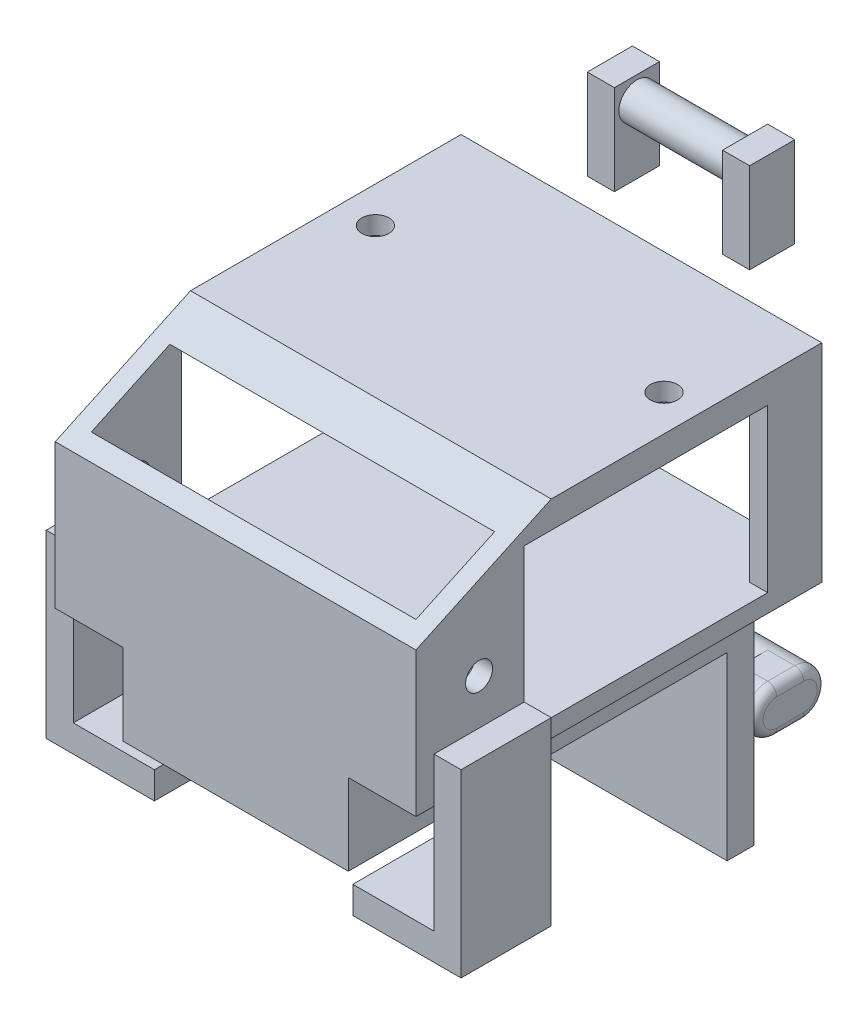
SolidWorks part; units mm, degrees
ref_plane "正面" through (0, 0, 0) normal (0, 0, 1) x (1, 0, 0)
ref_plane "平面" through (0, 0, 0) normal (0, 1, 0) x (1, 0, 0)
ref_plane "右側面" through (0, 0, 0) normal (1, 0, 0) x (0, 0, -1)
sketch "ｽｹｯﾁ1" plane through (0, 0, 0) normal (0, 1, 0) x (1, 0, 0)
  line L1 (0, 0) -> (25, 0)
  line L2 (0, 0) -> (0, 42)
  line L3 (0, 42) -> (25, 42)
  line L4 (25, 0) -> (25, 42)
  dimension "D1" = 25
  dimension "D2" = 42
extrude "ﾎﾞｽ - 押し出し1" add sketch "ｽｹｯﾁ1" along normal blind 9
sketch "ｽｹｯﾁ2" plane through (0, 0, -42) normal (0, 0, -1) x (-1, 0, 0)
  line L1 (-25, 9) -> (0, 9)
  line L2 (-25, 9) -> (-25, -20)
  line L3 (-25, -20) -> (0, -20)
  line L4 (0, 9) -> (0, -20)
  dimension "D1" = 29
extrude "ﾎﾞｽ - 押し出し2" add sketch "ｽｹｯﾁ2" along normal blind 3
sketch "ｽｹｯﾁ3" plane through (0, 9, 0) normal (0, 1, 0) x (1, 0, 0)
  line L1 (-7.5, 0) -> (32.5, 0)
  line L2 (-7.5, 0) -> (-7.5, 45)
  line L3 (-7.5, 45) -> (32.5, 45)
  line L4 (32.5, 0) -> (32.5, 45)
  line L5 (0, 0) -> (25, 0) construction
  line L6 (0, 45) -> (25, 45) construction
  line L7 (0, 45) -> (0, 0) construction
  dimension "D1" = 40
  dimension "D2" = 7.5
extrude "ﾎﾞｽ - 押し出し3" add sketch "ｽｹｯﾁ3" along normal blind 23
sketch "ｽｹｯﾁ4" plane through (0, 0, -45) normal (0, 0, -1) x (-1, 0, 0)
  line L0 (-32.5, 32) -> (7.5, 32) construction
  line L1 (5.5, 30) -> (-30.5, 30)
  line L2 (5.5, 30) -> (5.5, 11)
  line L3 (5.5, 11) -> (-30.5, 11)
  line L4 (-30.5, 30) -> (-30.5, 11)
  line L5 (7.5, 32) -> (7.5, 9) construction
  line L6 (-32.5, 32) -> (-32.5, 9) construction
  line L7 (0, 9) -> (7.5, 9) construction
  dimension "D1" = 2
  dimension "D2" = 2
  dimension "D3" = 2
  dimension "D4" = 2
extrude "ｶｯﾄ - 押し出し1" cut sketch "ｽｹｯﾁ4" against normal blind 43
sketch "ｽｹｯﾁ6" plane through (32.5, 0, 0) normal (1, 0, 0) x (0, 0, -1)
  line L0 (42, 0) -> (42, -20) construction
  line L1 (2, -6) -> (12, -6)
  line L2 (2, -6) -> (2, 14)
  line L3 (2, 14) -> (12, 14)
  line L4 (12, -6) -> (12, 14)
  line L5 (0, 9) -> (45, 9) construction
  dimension "D1" = 30
  dimension "D2" = 20
  dimension "D3" = 10
  dimension "D4" = 15
extrude "ﾎﾞｽ - 押し出し4" add sketch "ｽｹｯﾁ6" along normal blind 3
sketch "ｽｹｯﾁ7" plane through (0, -6, 0) normal (0, -1, 0) x (1, 0, 0)
  line L0 (35.5, -2) -> (32.5, -2) construction
  line L1 (32.5, -12) -> (23.5, -12)
  line L2 (32.5, -12) -> (32.5, -2)
  line L3 (32.5, -2) -> (23.5, -2)
  line L4 (23.5, -12) -> (23.5, -2)
  dimension "D1" = 9
extrude "ﾎﾞｽ - 押し出し5" add sketch "ｽｹｯﾁ7" against normal blind 3
ref_plane "平面1" through (12.5, 0, 0) normal (1, 0, 0) x (0, 0, -1)
mirror "ﾐﾗｰ1" about plane through (12.5, 0, 0) normal (1, 0, 0) of "ﾎﾞｽ - 押し出し4", "ﾎﾞｽ - 押し出し5"
sketch "ｽｹｯﾁ8" plane through (0, 32, 0) normal (0, 1, 0) x (1, 0, 0)
  line L0 (12.5, -15.95) -> (12.5, 15.95) construction
  line L1 (3.5, 53) -> (6.5, 53)
  line L2 (3.5, 53) -> (3.5, 48)
  line L3 (3.5, 48) -> (6.5, 48)
  line L4 (6.5, 53) -> (6.5, 48)
  line L5 (21.5, 48) -> (18.5, 48)
  line L6 (18.5, 53) -> (18.5, 48)
  line L7 (21.5, 53) -> (18.5, 53)
  line L8 (21.5, 53) -> (21.5, 48)
  line L10 (32.5, 45) -> (-7.5, 45) construction
  dimension "D1" = 5
  dimension "D2" = 3
  dimension "D3" = 12
  dimension "D4" = 8
extrude "ﾎﾞｽ - 押し出し6" add sketch "ｽｹｯﾁ8" along normal blind 10
sketch "ｽｹｯﾁ9" plane through (6.5, 0, 0) normal (1, 0, 0) x (0, 0, -1)
  line L0 (48, 42) -> (48, 32) construction
  line L1 (48, 42) -> (53, 42) construction
  circle A0 centre (50.5, 39.5) radius 2
  dimension "D1" = 4
  dimension "D2" = 2.5
  dimension "D3" = 2.5
extrude "ﾎﾞｽ - 押し出し7" add sketch "ｽｹｯﾁ9" along normal up to next (12 mm away)
sketch "ｽｹｯﾁ10" plane through (-7.5, 0, 0) normal (-1, 0, 0) x (0, 0, 1)
  line L0 (-2, 9) -> (0, 9) construction
  line L1 (0, 32) -> (0, 9) construction
  circle A0 centre (-7, 19) radius 1.5
  dimension "D1" = 3
  dimension "D2" = 10
  dimension "D3" = 7
extrude "ｶｯﾄ - 押し出し2" cut sketch "ｽｹｯﾁ10" against normal through all
sketch "ｽｹｯﾁ11" plane through (0, 0, -45) normal (0, 0, -1) x (-1, 0, 0)
  line L1 (-25, -20) -> (0, -20) construction
  line L2 (-12.5, 15.95) -> (-12.5, -15.95) construction
  circle A0 centre (-12.5, -10) radius 2.5
  dimension "D1" = 5
  dimension "D2" = 10
extrude "ﾎﾞｽ - 押し出し8" add sketch "ｽｹｯﾁ11" along normal blind 9
sketch "ｽｹｯﾁ12" plane through (12.5, 0, 0) normal (1, 0, 0) x (0, 0, -1)
  line L0 (45, -12.5) -> (45, -7.5) construction
  line L2 (45, -12.5) -> (54, -12.5) construction
  circle A0 centre (52, -10) radius 2.5
  dimension "D1" = 5
  dimension "D2" = 7
  dimension "D3" = 2.5
extrude "ﾎﾞｽ - 押し出し9" add sketch "ｽｹｯﾁ12" along normal blind 7
sketch "ｽｹｯﾁ13" plane through (19.5, 0, 0) normal (1, 0, 0) x (0, 0, -1)
  line L0 (52, -10) -> (49, -10) construction
  line L1 (52, -12.5) -> (49, -12.5)
  line L2 (52, -7.5) -> (49, -7.5)
  arc A0 (52, -12.5) -> (52, -7.5) centre (52, -10) ccw
  arc A1 (49, -7.5) -> (49, -12.5) centre (49, -10) ccw
  circle A2 centre (52, -10) radius 2.5 construction
  point P2 (50.5, -10)
  dimension "D1" = 2.5
  dimension "D2" = 3
extrude "ﾎﾞｽ - 押し出し10" add sketch "ｽｹｯﾁ13" along normal blind 4
fillet "ﾌｨﾚｯﾄ1" radius 1 4 edges at (23.5, -12.5, -50.5) (23.5, -10, -46.5) (23.5, -7.5, -50.5) (23.5, -10, -54.5)
mirror "ﾐﾗｰ2" about plane through (12.5, 0, 0) normal (1, 0, 0) of "ﾌｨﾚｯﾄ1", "ﾎﾞｽ - 押し出し10", "ﾎﾞｽ - 押し出し9"
sketch "ｽｹｯﾁ14" plane through (-7.5, 0, 0) normal (-1, 0, 0) x (0, 0, 1)
  line L0 (-15, 32) -> (0, 25)
  line L1 (-45, 32) -> (0, 32) construction
  line L2 (0, 32) -> (0, 9) construction
  line L3 (0, 25) -> (0, 32)
  line L4 (0, 32) -> (-15, 32)
  dimension "D1" = 15
  dimension "D2" = 7
extrude "ｶｯﾄ - 押し出し3" cut sketch "ｽｹｯﾁ14" against normal through all
sketch "ｽｹｯﾁ15" plane through (-7.5, 0, 0) normal (-1, 0, 0) x (0, 0, 1)
  line L0 (-45, 9) -> (-53, 32)
  line L1 (-53, 32) -> (-45, 32)
  line L2 (-45, 32) -> (-45, 9)
  dimension "D1" = 8
sketch "ｽｹｯﾁ19" plane through (30.5, 0, 0) normal (-1, 0, 0) x (0, 0, 1)
  line L0 (-2, 11) -> (-45, 11) construction
  line L1 (-39, 11) -> (-12, 11)
  line L2 (-39, 11) -> (-39, 29)
  line L3 (-39, 29) -> (-12, 29)
  line L4 (-12, 11) -> (-12, 29)
  line L5 (-2, 25.9333) -> (-2, 11) construction
  dimension "D1" = 27
  dimension "D2" = 10
  dimension "D3" = 18
extrude "ｶｯﾄ - 押し出し5" cut sketch "ｽｹｯﾁ19" against normal through all both and the other way through all
sketch "ｽｹｯﾁ20" plane through (0, 32, 0) normal (0, 1, 0) x (1, 0, 0)
  line L0 (-7.5, 45) -> (-7.5, 15) construction
  line L1 (32.5, 15) -> (32.5, 45) construction
  line L2 (3.5, 48) -> (6.5, 48) construction
  line L3 (18.5, 48) -> (21.5, 48) construction
  circle A0 centre (-3.5, 31.5) radius 1.5
  circle A1 centre (28.5, 31.5) radius 1.5
  dimension "D1" = 3
  dimension "D2" = 3
  dimension "D3" = 4
  dimension "D4" = 4
  dimension "D5" = 16.5
  dimension "D6" = 16.5
extrude "ｶｯﾄ - 押し出し6" cut sketch "ｽｹｯﾁ20" against normal blind 10 and the other way through all
sketch "ｽｹｯﾁ21" plane through (0, 30, 0) normal (0, -1, 0) x (1, 0, 0)
  line L0 (-5.5, -45) -> (30.5, -45) construction
  line L1 (-5.5, -10.7143) -> (-5.5, -45) construction
  line L2 (22.5, -45) -> (19.5, -45)
  line L3 (22.5, -45) -> (22.5, -40)
  line L4 (22.5, -40) -> (19.5, -40)
  line L5 (19.5, -45) -> (19.5, -40)
  line L6 (5.5, -45) -> (2.5, -45)
  line L7 (5.5, -45) -> (5.5, -40)
  line L8 (5.5, -40) -> (2.5, -40)
  line L9 (2.5, -45) -> (2.5, -40)
  dimension "D1" = 3
  dimension "D2" = 5
  dimension "D3" = 3
  dimension "D4" = 5
  dimension "D5" = 8
  dimension "D6" = 8
extrude "ﾎﾞｽ - 押し出し11" add sketch "ｽｹｯﾁ21" along normal blind 10
sketch "ｽｹｯﾁ22" plane through (19.5, 0, 0) normal (-1, 0, 0) x (0, 0, 1)
  line L0 (-40, 20) -> (-45, 20) construction
  line L1 (-40, 20) -> (-40, 30) construction
  circle A0 centre (-42.5, 22.5) radius 2.5
  dimension "D1" = 5
  dimension "D2" = 2.5
  dimension "D3" = 2.5
extrude "ﾎﾞｽ - 押し出し12" add sketch "ｽｹｯﾁ22" along normal up to next
